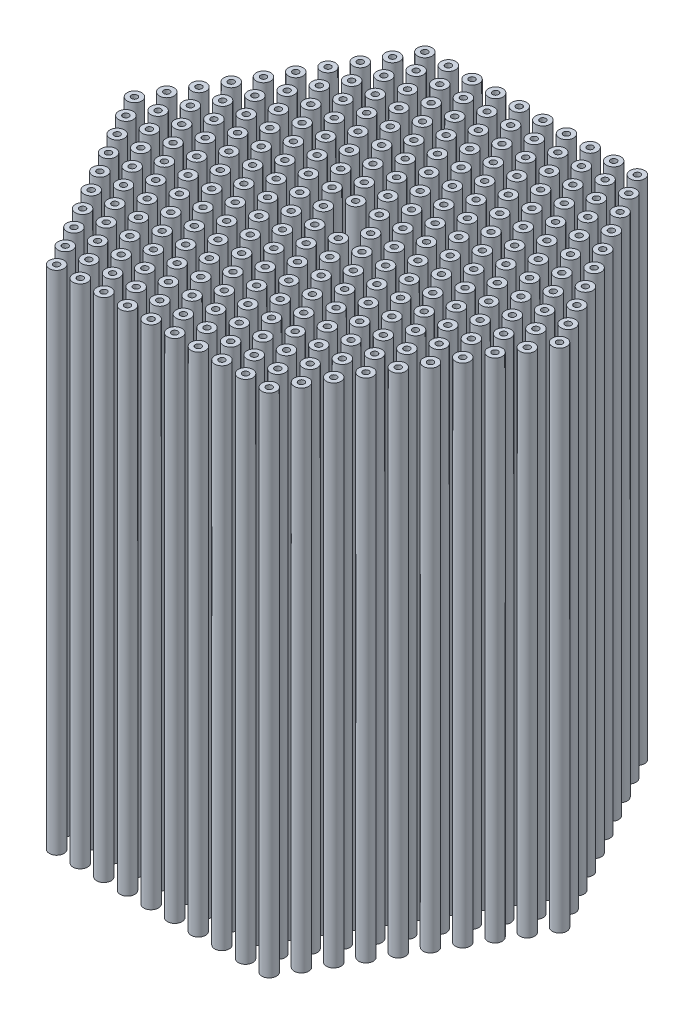
SolidWorks part; units mm, degrees
material "Chumbo puro"
ref_plane "Plano frontal" through (0, 0, 0) normal (0, 0, 1) x (1, 0, 0)
ref_plane "Plano superior" through (0, 0, 0) normal (0, 1, 0) x (1, 0, 0)
ref_plane "Plano direito" through (0, 0, 0) normal (1, 0, 0) x (0, 0, -1)
sketch "Esboço1" plane through (0, 0, 0) normal (0, 1, 0) x (1, 0, 0)
  line L0 (0, -642.4629) -> (0, 642.4629) construction
  line L1 (-577.4118, 0) -> (577.4118, 0) construction
  circle A0 centre (0, 0) radius 6.35 construction
  circle A1 centre (0, 0) radius 15.35 construction
  circle A2 centre (0, 0) radius 25 construction
  circle A23 centre (-25, 43.3013) radius 6.35
  circle A26 centre (-25, 43.3013) radius 15.35
  circle A29 centre (-25, 43.3013) radius 25 construction
  circle A50 centre (0, 86.6025) radius 6.35
  circle A53 centre (0, 86.6025) radius 15.35
  circle A56 centre (0, 86.6025) radius 25 construction
  circle A59 centre (-25, 129.9038) radius 6.35
  circle A62 centre (-25, 129.9038) radius 15.35
  circle A65 centre (-25, 129.9038) radius 25 construction
  circle A68 centre (25, 129.9038) radius 6.35
  circle A71 centre (25, 129.9038) radius 15.35
  circle A74 centre (25, 129.9038) radius 25 construction
  circle A77 centre (0, 173.2051) radius 6.35
  circle A80 centre (0, 173.2051) radius 15.35
  circle A83 centre (0, 173.2051) radius 25 construction
  circle A86 centre (-25, 216.5064) radius 6.35
  circle A87 centre (25, 43.3013) radius 6.35
  circle A88 centre (25, 43.3013) radius 15.35
  circle A89 centre (25, 43.3013) radius 25 construction
  circle A93 centre (-25, 216.5064) radius 15.35
  circle A94 centre (-25, 216.5064) radius 25 construction
  circle A95 centre (25, 216.5064) radius 6.35
  circle A96 centre (25, 216.5064) radius 15.35
  circle A97 centre (25, 216.5064) radius 25 construction
  circle A98 centre (0, 259.8076) radius 6.35
  circle A99 centre (0, 259.8076) radius 15.35
  circle A100 centre (0, 259.8076) radius 25 construction
  circle A101 centre (-25, 303.1089) radius 6.35
  circle A102 centre (-25, 303.1089) radius 15.35
  circle A103 centre (-25, 303.1089) radius 25 construction
  circle A104 centre (25, 303.1089) radius 6.35
  circle A105 centre (25, 303.1089) radius 15.35
  circle A106 centre (25, 303.1089) radius 25 construction
  circle A107 centre (0, 346.4102) radius 6.35
  circle A108 centre (0, 346.4102) radius 15.35
  circle A109 centre (0, 346.4102) radius 25 construction
  circle A110 centre (-25, 389.7114) radius 6.35
  circle A111 centre (-25, 389.7114) radius 15.35
  circle A112 centre (-25, 389.7114) radius 25 construction
  circle A113 centre (25, 389.7114) radius 6.35
  circle A114 centre (25, 389.7114) radius 15.35
  circle A115 centre (25, 389.7114) radius 25 construction
  circle A167 centre (50, 0) radius 15.35
  circle A168 centre (50, 0) radius 6.35
  circle A169 centre (100, 0) radius 15.35
  circle A170 centre (100, 0) radius 6.35
  circle A171 centre (150, 0) radius 15.35
  circle A172 centre (150, 0) radius 6.35
  circle A173 centre (200, 0) radius 15.35
  circle A174 centre (200, 0) radius 6.35
  circle A175 centre (250, 0) radius 15.35
  circle A176 centre (250, 0) radius 6.35
  circle A177 centre (300, 0) radius 15.35
  circle A178 centre (300, 0) radius 6.35
  circle A179 centre (350, 0) radius 15.35
  circle A180 centre (350, 0) radius 6.35
  circle A181 centre (400, 0) radius 15.35
  circle A182 centre (400, 0) radius 6.35
  circle A183 centre (450, 0) radius 15.35
  circle A184 centre (450, 0) radius 6.35
  circle A185 centre (-50, 0) radius 15.35
  circle A186 centre (-50, 0) radius 6.35
  circle A187 centre (-100, 0) radius 15.35
  circle A188 centre (-100, 0) radius 6.35
  circle A189 centre (-150, 0) radius 15.35
  circle A190 centre (-150, 0) radius 6.35
  circle A191 centre (-200, 0) radius 15.35
  circle A192 centre (-200, 0) radius 6.35
  circle A193 centre (-250, 0) radius 15.35
  circle A194 centre (-250, 0) radius 6.35
  circle A195 centre (-300, 0) radius 15.35
  circle A196 centre (-300, 0) radius 6.35
  circle A197 centre (-350, 0) radius 15.35
  circle A198 centre (-350, 0) radius 6.35
  circle A199 centre (-400, 0) radius 15.35
  circle A200 centre (-400, 0) radius 6.35
  circle A201 centre (-450, 0) radius 15.35
  circle A202 centre (-450, 0) radius 6.35
  circle A203 centre (75, 43.3013) radius 15.35
  circle A204 centre (75, 43.3013) radius 6.35
  circle A205 centre (125, 43.3013) radius 15.35
  circle A206 centre (125, 43.3013) radius 6.35
  circle A207 centre (175, 43.3013) radius 15.35
  circle A208 centre (175, 43.3013) radius 6.35
  circle A209 centre (225, 43.3013) radius 15.35
  circle A210 centre (225, 43.3013) radius 6.35
  circle A211 centre (275, 43.3013) radius 15.35
  circle A212 centre (275, 43.3013) radius 6.35
  circle A213 centre (325, 43.3013) radius 15.35
  circle A214 centre (325, 43.3013) radius 6.35
  circle A215 centre (375, 43.3013) radius 15.35
  circle A216 centre (375, 43.3013) radius 6.35
  circle A217 centre (425, 43.3013) radius 15.35
  circle A218 centre (425, 43.3013) radius 6.35
  circle A235 centre (50, 86.6025) radius 6.35
  circle A236 centre (50, 86.6025) radius 15.35
  circle A237 centre (100, 86.6025) radius 6.35
  circle A238 centre (100, 86.6025) radius 15.35
  circle A239 centre (150, 86.6025) radius 6.35
  circle A240 centre (150, 86.6025) radius 15.35
  circle A241 centre (200, 86.6025) radius 6.35
  circle A242 centre (200, 86.6025) radius 15.35
  circle A243 centre (250, 86.6025) radius 6.35
  circle A244 centre (250, 86.6025) radius 15.35
  circle A245 centre (300, 86.6025) radius 6.35
  circle A246 centre (300, 86.6025) radius 15.35
  circle A247 centre (350, 86.6025) radius 6.35
  circle A248 centre (350, 86.6025) radius 15.35
  circle A249 centre (400, 86.6025) radius 6.35
  circle A250 centre (400, 86.6025) radius 15.35
  circle A251 centre (75, 129.9038) radius 6.35
  circle A252 centre (75, 129.9038) radius 15.35
  circle A253 centre (125, 129.9038) radius 6.35
  circle A254 centre (125, 129.9038) radius 15.35
  circle A255 centre (175, 129.9038) radius 6.35
  circle A256 centre (175, 129.9038) radius 15.35
  circle A257 centre (225, 129.9038) radius 6.35
  circle A258 centre (225, 129.9038) radius 15.35
  circle A259 centre (275, 129.9038) radius 6.35
  circle A260 centre (275, 129.9038) radius 15.35
  circle A261 centre (325, 129.9038) radius 6.35
  circle A262 centre (325, 129.9038) radius 15.35
  circle A263 centre (375, 129.9038) radius 6.35
  circle A264 centre (375, 129.9038) radius 15.35
  circle A265 centre (50, 173.2051) radius 15.35
  circle A266 centre (50, 173.2051) radius 6.35
  circle A267 centre (100, 173.2051) radius 15.35
  circle A268 centre (100, 173.2051) radius 6.35
  circle A269 centre (150, 173.2051) radius 15.35
  circle A270 centre (150, 173.2051) radius 6.35
  circle A271 centre (200, 173.2051) radius 15.35
  circle A272 centre (200, 173.2051) radius 6.35
  circle A273 centre (250, 173.2051) radius 15.35
  circle A274 centre (250, 173.2051) radius 6.35
  circle A275 centre (300, 173.2051) radius 15.35
  circle A276 centre (300, 173.2051) radius 6.35
  circle A277 centre (350, 173.2051) radius 15.35
  circle A278 centre (350, 173.2051) radius 6.35
  circle A279 centre (75, 216.5064) radius 6.35
  circle A280 centre (75, 216.5064) radius 15.35
  circle A281 centre (125, 216.5064) radius 6.35
  circle A282 centre (125, 216.5064) radius 15.35
  circle A283 centre (175, 216.5064) radius 6.35
  circle A284 centre (175, 216.5064) radius 15.35
  circle A285 centre (225, 216.5064) radius 6.35
  circle A286 centre (225, 216.5064) radius 15.35
  circle A287 centre (275, 216.5064) radius 6.35
  circle A288 centre (275, 216.5064) radius 15.35
  circle A289 centre (325, 216.5064) radius 6.35
  circle A290 centre (325, 216.5064) radius 15.35
  circle A291 centre (50, 259.8076) radius 6.35
  circle A292 centre (50, 259.8076) radius 15.35
  circle A293 centre (100, 259.8076) radius 6.35
  circle A294 centre (100, 259.8076) radius 15.35
  circle A295 centre (150, 259.8076) radius 6.35
  circle A296 centre (150, 259.8076) radius 15.35
  circle A297 centre (200, 259.8076) radius 6.35
  circle A298 centre (200, 259.8076) radius 15.35
  circle A299 centre (250, 259.8076) radius 6.35
  circle A300 centre (250, 259.8076) radius 15.35
  circle A301 centre (300, 259.8076) radius 6.35
  circle A302 centre (300, 259.8076) radius 15.35
  circle A303 centre (75, 303.1089) radius 6.35
  circle A304 centre (75, 303.1089) radius 15.35
  circle A305 centre (125, 303.1089) radius 6.35
  circle A306 centre (125, 303.1089) radius 15.35
  circle A307 centre (175, 303.1089) radius 6.35
  circle A308 centre (175, 303.1089) radius 15.35
  circle A309 centre (225, 303.1089) radius 6.35
  circle A310 centre (225, 303.1089) radius 15.35
  circle A311 centre (275, 303.1089) radius 6.35
  circle A312 centre (275, 303.1089) radius 15.35
  circle A313 centre (50, 346.4102) radius 6.35
  circle A314 centre (50, 346.4102) radius 15.35
  circle A315 centre (100, 346.4102) radius 6.35
  circle A316 centre (100, 346.4102) radius 15.35
  circle A317 centre (150, 346.4102) radius 6.35
  circle A318 centre (150, 346.4102) radius 15.35
  circle A319 centre (200, 346.4102) radius 6.35
  circle A320 centre (200, 346.4102) radius 15.35
  circle A321 centre (250, 346.4102) radius 6.35
  circle A322 centre (250, 346.4102) radius 15.35
  circle A323 centre (75, 389.7114) radius 6.35
  circle A324 centre (75, 389.7114) radius 15.35
  circle A325 centre (125, 389.7114) radius 6.35
  circle A326 centre (125, 389.7114) radius 15.35
  circle A327 centre (175, 389.7114) radius 6.35
  circle A328 centre (175, 389.7114) radius 15.35
  circle A329 centre (225, 389.7114) radius 6.35
  circle A330 centre (225, 389.7114) radius 15.35
  circle A331 centre (-225, 389.7114) radius 15.35
  circle A332 centre (-225, 389.7114) radius 6.35
  circle A333 centre (-175, 389.7114) radius 15.35
  circle A334 centre (-175, 389.7114) radius 6.35
  circle A335 centre (-125, 389.7114) radius 15.35
  circle A336 centre (-125, 389.7114) radius 6.35
  circle A337 centre (-75, 389.7114) radius 15.35
  circle A338 centre (-75, 389.7114) radius 6.35
  circle A339 centre (-250, 346.4102) radius 15.35
  circle A340 centre (-250, 346.4102) radius 6.35
  circle A341 centre (-200, 346.4102) radius 15.35
  circle A342 centre (-200, 346.4102) radius 6.35
  circle A343 centre (-150, 346.4102) radius 15.35
  circle A344 centre (-150, 346.4102) radius 6.35
  circle A345 centre (-100, 346.4102) radius 15.35
  circle A346 centre (-100, 346.4102) radius 6.35
  circle A347 centre (-50, 346.4102) radius 15.35
  circle A348 centre (-50, 346.4102) radius 6.35
  circle A349 centre (-275, 303.1089) radius 15.35
  circle A350 centre (-275, 303.1089) radius 6.35
  circle A351 centre (-225, 303.1089) radius 15.35
  circle A352 centre (-225, 303.1089) radius 6.35
  circle A353 centre (-175, 303.1089) radius 15.35
  circle A354 centre (-175, 303.1089) radius 6.35
  circle A355 centre (-125, 303.1089) radius 15.35
  circle A356 centre (-125, 303.1089) radius 6.35
  circle A357 centre (-75, 303.1089) radius 15.35
  circle A358 centre (-75, 303.1089) radius 6.35
  circle A359 centre (-300, 259.8076) radius 15.35
  circle A360 centre (-300, 259.8076) radius 6.35
  circle A361 centre (-250, 259.8076) radius 15.35
  circle A362 centre (-250, 259.8076) radius 6.35
  circle A363 centre (-200, 259.8076) radius 15.35
  circle A364 centre (-200, 259.8076) radius 6.35
  circle A365 centre (-150, 259.8076) radius 15.35
  circle A366 centre (-150, 259.8076) radius 6.35
  circle A367 centre (-100, 259.8076) radius 15.35
  circle A368 centre (-100, 259.8076) radius 6.35
  circle A369 centre (-50, 259.8076) radius 15.35
  circle A370 centre (-50, 259.8076) radius 6.35
  circle A371 centre (-325, 216.5064) radius 15.35
  circle A372 centre (-325, 216.5064) radius 6.35
  circle A373 centre (-275, 216.5064) radius 15.35
  circle A374 centre (-275, 216.5064) radius 6.35
  circle A375 centre (-225, 216.5064) radius 15.35
  circle A376 centre (-225, 216.5064) radius 6.35
  circle A377 centre (-175, 216.5064) radius 15.35
  circle A378 centre (-175, 216.5064) radius 6.35
  circle A379 centre (-125, 216.5064) radius 15.35
  circle A380 centre (-125, 216.5064) radius 6.35
  circle A381 centre (-75, 216.5064) radius 15.35
  circle A382 centre (-75, 216.5064) radius 6.35
  circle A383 centre (-350, 173.2051) radius 6.35
  circle A384 centre (-350, 173.2051) radius 15.35
  circle A385 centre (-300, 173.2051) radius 6.35
  circle A386 centre (-300, 173.2051) radius 15.35
  circle A387 centre (-250, 173.2051) radius 6.35
  circle A388 centre (-250, 173.2051) radius 15.35
  circle A389 centre (-200, 173.2051) radius 6.35
  circle A390 centre (-200, 173.2051) radius 15.35
  circle A391 centre (-150, 173.2051) radius 6.35
  circle A392 centre (-150, 173.2051) radius 15.35
  circle A393 centre (-100, 173.2051) radius 6.35
  circle A394 centre (-100, 173.2051) radius 15.35
  circle A395 centre (-50, 173.2051) radius 6.35
  circle A396 centre (-50, 173.2051) radius 15.35
  circle A397 centre (-375, 129.9038) radius 15.35
  circle A398 centre (-375, 129.9038) radius 6.35
  circle A399 centre (-325, 129.9038) radius 15.35
  circle A400 centre (-325, 129.9038) radius 6.35
  circle A401 centre (-275, 129.9038) radius 15.35
  circle A402 centre (-275, 129.9038) radius 6.35
  circle A403 centre (-225, 129.9038) radius 15.35
  circle A404 centre (-225, 129.9038) radius 6.35
  circle A405 centre (-175, 129.9038) radius 15.35
  circle A406 centre (-175, 129.9038) radius 6.35
  circle A407 centre (-125, 129.9038) radius 15.35
  circle A408 centre (-125, 129.9038) radius 6.35
  circle A409 centre (-75, 129.9038) radius 15.35
  circle A410 centre (-75, 129.9038) radius 6.35
  circle A411 centre (-400, 86.6025) radius 15.35
  circle A412 centre (-400, 86.6025) radius 6.35
  circle A413 centre (-350, 86.6025) radius 15.35
  circle A414 centre (-350, 86.6025) radius 6.35
  circle A415 centre (-300, 86.6025) radius 15.35
  circle A416 centre (-300, 86.6025) radius 6.35
  circle A417 centre (-250, 86.6025) radius 15.35
  circle A418 centre (-250, 86.6025) radius 6.35
  circle A419 centre (-200, 86.6025) radius 15.35
  circle A420 centre (-200, 86.6025) radius 6.35
  circle A421 centre (-150, 86.6025) radius 15.35
  circle A422 centre (-150, 86.6025) radius 6.35
  circle A423 centre (-100, 86.6025) radius 15.35
  circle A424 centre (-100, 86.6025) radius 6.35
  circle A425 centre (-50, 86.6025) radius 15.35
  circle A426 centre (-50, 86.6025) radius 6.35
  circle A427 centre (-425, 43.3013) radius 6.35
  circle A428 centre (-425, 43.3013) radius 15.35
  circle A429 centre (-375, 43.3013) radius 6.35
  circle A430 centre (-375, 43.3013) radius 15.35
  circle A431 centre (-325, 43.3013) radius 6.35
  circle A432 centre (-325, 43.3013) radius 15.35
  circle A433 centre (-275, 43.3013) radius 6.35
  circle A434 centre (-275, 43.3013) radius 15.35
  circle A435 centre (-225, 43.3013) radius 6.35
  circle A436 centre (-225, 43.3013) radius 15.35
  circle A437 centre (-175, 43.3013) radius 6.35
  circle A438 centre (-175, 43.3013) radius 15.35
  circle A439 centre (-125, 43.3013) radius 6.35
  circle A440 centre (-125, 43.3013) radius 15.35
  circle A441 centre (-75, 43.3013) radius 6.35
  circle A442 centre (-75, 43.3013) radius 15.35
  circle A443 centre (-25, -43.3013) radius 25 construction
  circle A444 centre (25, -43.3013) radius 25 construction
  circle A445 centre (25, -389.7114) radius 25 construction
  circle A446 centre (-25, -389.7114) radius 25 construction
  circle A447 centre (0, -346.4102) radius 25 construction
  circle A448 centre (25, -303.1089) radius 25 construction
  circle A449 centre (-25, -303.1089) radius 25 construction
  circle A450 centre (0, -259.8076) radius 25 construction
  circle A451 centre (25, -216.5064) radius 25 construction
  circle A452 centre (-25, -216.5064) radius 25 construction
  circle A453 centre (0, -173.2051) radius 25 construction
  circle A454 centre (25, -129.9038) radius 25 construction
  circle A455 centre (-25, -129.9038) radius 25 construction
  circle A456 centre (0, -86.6025) radius 25 construction
  circle A457 centre (-75, -43.3013) radius 15.35
  circle A458 centre (-75, -43.3013) radius 6.35
  circle A459 centre (-125, -43.3013) radius 15.35
  circle A460 centre (-125, -43.3013) radius 6.35
  circle A461 centre (-175, -43.3013) radius 15.35
  circle A462 centre (-175, -43.3013) radius 6.35
  circle A463 centre (-225, -43.3013) radius 15.35
  circle A464 centre (-225, -43.3013) radius 6.35
  circle A465 centre (-275, -43.3013) radius 15.35
  circle A466 centre (-275, -43.3013) radius 6.35
  circle A467 centre (-325, -43.3013) radius 15.35
  circle A468 centre (-325, -43.3013) radius 6.35
  circle A469 centre (-375, -43.3013) radius 15.35
  circle A470 centre (-375, -43.3013) radius 6.35
  circle A471 centre (-425, -43.3013) radius 15.35
  circle A472 centre (-425, -43.3013) radius 6.35
  circle A473 centre (-50, -86.6025) radius 6.35
  circle A474 centre (-50, -86.6025) radius 15.35
  circle A475 centre (-100, -86.6025) radius 6.35
  circle A476 centre (-100, -86.6025) radius 15.35
  circle A477 centre (-150, -86.6025) radius 6.35
  circle A478 centre (-150, -86.6025) radius 15.35
  circle A479 centre (-200, -86.6025) radius 6.35
  circle A480 centre (-200, -86.6025) radius 15.35
  circle A481 centre (-250, -86.6025) radius 6.35
  circle A482 centre (-250, -86.6025) radius 15.35
  circle A483 centre (-300, -86.6025) radius 6.35
  circle A484 centre (-300, -86.6025) radius 15.35
  circle A485 centre (-350, -86.6025) radius 6.35
  circle A486 centre (-350, -86.6025) radius 15.35
  circle A487 centre (-400, -86.6025) radius 6.35
  circle A488 centre (-400, -86.6025) radius 15.35
  circle A489 centre (-75, -129.9038) radius 6.35
  circle A490 centre (-75, -129.9038) radius 15.35
  circle A491 centre (-125, -129.9038) radius 6.35
  circle A492 centre (-125, -129.9038) radius 15.35
  circle A493 centre (-175, -129.9038) radius 6.35
  circle A494 centre (-175, -129.9038) radius 15.35
  circle A495 centre (-225, -129.9038) radius 6.35
  circle A496 centre (-225, -129.9038) radius 15.35
  circle A497 centre (-275, -129.9038) radius 6.35
  circle A498 centre (-275, -129.9038) radius 15.35
  circle A499 centre (-325, -129.9038) radius 6.35
  circle A500 centre (-325, -129.9038) radius 15.35
  circle A501 centre (-375, -129.9038) radius 6.35
  circle A502 centre (-375, -129.9038) radius 15.35
  circle A503 centre (-50, -173.2051) radius 15.35
  circle A504 centre (-50, -173.2051) radius 6.35
  circle A505 centre (-100, -173.2051) radius 15.35
  circle A506 centre (-100, -173.2051) radius 6.35
  circle A507 centre (-150, -173.2051) radius 15.35
  circle A508 centre (-150, -173.2051) radius 6.35
  circle A509 centre (-200, -173.2051) radius 15.35
  circle A510 centre (-200, -173.2051) radius 6.35
  circle A511 centre (-250, -173.2051) radius 15.35
  circle A512 centre (-250, -173.2051) radius 6.35
  circle A513 centre (-300, -173.2051) radius 15.35
  circle A514 centre (-300, -173.2051) radius 6.35
  circle A515 centre (-350, -173.2051) radius 15.35
  circle A516 centre (-350, -173.2051) radius 6.35
  circle A517 centre (-75, -216.5064) radius 6.35
  circle A518 centre (-75, -216.5064) radius 15.35
  circle A519 centre (-125, -216.5064) radius 6.35
  circle A520 centre (-125, -216.5064) radius 15.35
  circle A521 centre (-175, -216.5064) radius 6.35
  circle A522 centre (-175, -216.5064) radius 15.35
  circle A523 centre (-225, -216.5064) radius 6.35
  circle A524 centre (-225, -216.5064) radius 15.35
  circle A525 centre (-275, -216.5064) radius 6.35
  circle A526 centre (-275, -216.5064) radius 15.35
  circle A527 centre (-325, -216.5064) radius 6.35
  circle A528 centre (-325, -216.5064) radius 15.35
  circle A529 centre (-50, -259.8076) radius 6.35
  circle A530 centre (-50, -259.8076) radius 15.35
  circle A531 centre (-100, -259.8076) radius 6.35
  circle A532 centre (-100, -259.8076) radius 15.35
  circle A533 centre (-150, -259.8076) radius 6.35
  circle A534 centre (-150, -259.8076) radius 15.35
  circle A535 centre (-200, -259.8076) radius 6.35
  circle A536 centre (-200, -259.8076) radius 15.35
  circle A537 centre (-250, -259.8076) radius 6.35
  circle A538 centre (-250, -259.8076) radius 15.35
  circle A539 centre (-300, -259.8076) radius 6.35
  circle A540 centre (-300, -259.8076) radius 15.35
  circle A541 centre (-75, -303.1089) radius 6.35
  circle A542 centre (-75, -303.1089) radius 15.35
  circle A543 centre (-125, -303.1089) radius 6.35
  circle A544 centre (-125, -303.1089) radius 15.35
  circle A545 centre (-175, -303.1089) radius 6.35
  circle A546 centre (-175, -303.1089) radius 15.35
  circle A547 centre (-225, -303.1089) radius 6.35
  circle A548 centre (-225, -303.1089) radius 15.35
  circle A549 centre (-275, -303.1089) radius 6.35
  circle A550 centre (-275, -303.1089) radius 15.35
  circle A551 centre (-50, -346.4102) radius 6.35
  circle A552 centre (-50, -346.4102) radius 15.35
  circle A553 centre (-100, -346.4102) radius 6.35
  circle A554 centre (-100, -346.4102) radius 15.35
  circle A555 centre (-150, -346.4102) radius 6.35
  circle A556 centre (-150, -346.4102) radius 15.35
  circle A557 centre (-200, -346.4102) radius 6.35
  circle A558 centre (-200, -346.4102) radius 15.35
  circle A559 centre (-250, -346.4102) radius 6.35
  circle A560 centre (-250, -346.4102) radius 15.35
  circle A561 centre (-75, -389.7114) radius 6.35
  circle A562 centre (-75, -389.7114) radius 15.35
  circle A563 centre (-125, -389.7114) radius 6.35
  circle A564 centre (-125, -389.7114) radius 15.35
  circle A565 centre (-175, -389.7114) radius 6.35
  circle A566 centre (-175, -389.7114) radius 15.35
  circle A567 centre (-225, -389.7114) radius 6.35
  circle A568 centre (-225, -389.7114) radius 15.35
  circle A569 centre (225, -389.7114) radius 15.35
  circle A570 centre (225, -389.7114) radius 6.35
  circle A571 centre (175, -389.7114) radius 15.35
  circle A572 centre (175, -389.7114) radius 6.35
  circle A573 centre (125, -389.7114) radius 15.35
  circle A574 centre (125, -389.7114) radius 6.35
  circle A575 centre (75, -389.7114) radius 15.35
  circle A576 centre (75, -389.7114) radius 6.35
  circle A577 centre (250, -346.4102) radius 15.35
  circle A578 centre (250, -346.4102) radius 6.35
  circle A579 centre (200, -346.4102) radius 15.35
  circle A580 centre (200, -346.4102) radius 6.35
  circle A581 centre (150, -346.4102) radius 15.35
  circle A582 centre (150, -346.4102) radius 6.35
  circle A583 centre (100, -346.4102) radius 15.35
  circle A584 centre (100, -346.4102) radius 6.35
  circle A585 centre (50, -346.4102) radius 15.35
  circle A586 centre (50, -346.4102) radius 6.35
  circle A587 centre (275, -303.1089) radius 15.35
  circle A588 centre (275, -303.1089) radius 6.35
  circle A589 centre (225, -303.1089) radius 15.35
  circle A590 centre (225, -303.1089) radius 6.35
  circle A591 centre (175, -303.1089) radius 15.35
  circle A592 centre (175, -303.1089) radius 6.35
  circle A593 centre (125, -303.1089) radius 15.35
  circle A594 centre (125, -303.1089) radius 6.35
  circle A595 centre (75, -303.1089) radius 15.35
  circle A596 centre (75, -303.1089) radius 6.35
  circle A597 centre (300, -259.8076) radius 15.35
  circle A598 centre (300, -259.8076) radius 6.35
  circle A599 centre (250, -259.8076) radius 15.35
  circle A600 centre (250, -259.8076) radius 6.35
  circle A601 centre (200, -259.8076) radius 15.35
  circle A602 centre (200, -259.8076) radius 6.35
  circle A603 centre (150, -259.8076) radius 15.35
  circle A604 centre (150, -259.8076) radius 6.35
  circle A605 centre (100, -259.8076) radius 15.35
  circle A606 centre (100, -259.8076) radius 6.35
  circle A607 centre (50, -259.8076) radius 15.35
  circle A608 centre (50, -259.8076) radius 6.35
  circle A609 centre (325, -216.5064) radius 15.35
  circle A610 centre (325, -216.5064) radius 6.35
  circle A611 centre (275, -216.5064) radius 15.35
  circle A612 centre (275, -216.5064) radius 6.35
  circle A613 centre (225, -216.5064) radius 15.35
  circle A614 centre (225, -216.5064) radius 6.35
  circle A615 centre (175, -216.5064) radius 15.35
  circle A616 centre (175, -216.5064) radius 6.35
  circle A617 centre (125, -216.5064) radius 15.35
  circle A618 centre (125, -216.5064) radius 6.35
  circle A619 centre (75, -216.5064) radius 15.35
  circle A620 centre (75, -216.5064) radius 6.35
  circle A621 centre (350, -173.2051) radius 6.35
  circle A622 centre (350, -173.2051) radius 15.35
  circle A623 centre (300, -173.2051) radius 6.35
  circle A624 centre (300, -173.2051) radius 15.35
  circle A625 centre (250, -173.2051) radius 6.35
  circle A626 centre (250, -173.2051) radius 15.35
  circle A627 centre (200, -173.2051) radius 6.35
  circle A628 centre (200, -173.2051) radius 15.35
  circle A629 centre (150, -173.2051) radius 6.35
  circle A630 centre (150, -173.2051) radius 15.35
  circle A631 centre (100, -173.2051) radius 6.35
  circle A632 centre (100, -173.2051) radius 15.35
  circle A633 centre (50, -173.2051) radius 6.35
  circle A634 centre (50, -173.2051) radius 15.35
  circle A635 centre (375, -129.9038) radius 15.35
  circle A636 centre (375, -129.9038) radius 6.35
  circle A637 centre (325, -129.9038) radius 15.35
  circle A638 centre (325, -129.9038) radius 6.35
  circle A639 centre (275, -129.9038) radius 15.35
  circle A640 centre (275, -129.9038) radius 6.35
  circle A641 centre (225, -129.9038) radius 15.35
  circle A642 centre (225, -129.9038) radius 6.35
  circle A643 centre (175, -129.9038) radius 15.35
  circle A644 centre (175, -129.9038) radius 6.35
  circle A645 centre (125, -129.9038) radius 15.35
  circle A646 centre (125, -129.9038) radius 6.35
  circle A647 centre (75, -129.9038) radius 15.35
  circle A648 centre (75, -129.9038) radius 6.35
  circle A649 centre (400, -86.6025) radius 15.35
  circle A650 centre (400, -86.6025) radius 6.35
  circle A651 centre (350, -86.6025) radius 15.35
  circle A652 centre (350, -86.6025) radius 6.35
  circle A653 centre (300, -86.6025) radius 15.35
  circle A654 centre (300, -86.6025) radius 6.35
  circle A655 centre (250, -86.6025) radius 15.35
  circle A656 centre (250, -86.6025) radius 6.35
  circle A657 centre (200, -86.6025) radius 15.35
  circle A658 centre (200, -86.6025) radius 6.35
  circle A659 centre (150, -86.6025) radius 15.35
  circle A660 centre (150, -86.6025) radius 6.35
  circle A661 centre (100, -86.6025) radius 15.35
  circle A662 centre (100, -86.6025) radius 6.35
  circle A663 centre (50, -86.6025) radius 15.35
  circle A664 centre (50, -86.6025) radius 6.35
  circle A665 centre (425, -43.3013) radius 6.35
  circle A666 centre (425, -43.3013) radius 15.35
  circle A667 centre (375, -43.3013) radius 6.35
  circle A668 centre (375, -43.3013) radius 15.35
  circle A669 centre (325, -43.3013) radius 6.35
  circle A670 centre (325, -43.3013) radius 15.35
  circle A671 centre (275, -43.3013) radius 6.35
  circle A672 centre (275, -43.3013) radius 15.35
  circle A673 centre (225, -43.3013) radius 6.35
  circle A674 centre (225, -43.3013) radius 15.35
  circle A675 centre (175, -43.3013) radius 6.35
  circle A676 centre (175, -43.3013) radius 15.35
  circle A677 centre (125, -43.3013) radius 6.35
  circle A678 centre (125, -43.3013) radius 15.35
  circle A679 centre (75, -43.3013) radius 6.35
  circle A680 centre (75, -43.3013) radius 15.35
  circle A681 centre (25, -389.7114) radius 15.35
  circle A682 centre (25, -389.7114) radius 6.35
  circle A683 centre (-25, -389.7114) radius 15.35
  circle A684 centre (-25, -389.7114) radius 6.35
  circle A685 centre (0, -346.4102) radius 15.35
  circle A686 centre (0, -346.4102) radius 6.35
  circle A687 centre (25, -303.1089) radius 15.35
  circle A688 centre (25, -303.1089) radius 6.35
  circle A689 centre (-25, -303.1089) radius 15.35
  circle A690 centre (-25, -303.1089) radius 6.35
  circle A691 centre (0, -259.8076) radius 15.35
  circle A692 centre (0, -259.8076) radius 6.35
  circle A693 centre (25, -216.5064) radius 15.35
  circle A694 centre (25, -216.5064) radius 6.35
  circle A695 centre (-25, -216.5064) radius 15.35
  circle A696 centre (25, -43.3013) radius 15.35
  circle A697 centre (25, -43.3013) radius 6.35
  circle A698 centre (-25, -216.5064) radius 6.35
  circle A699 centre (0, -173.2051) radius 15.35
  circle A700 centre (0, -173.2051) radius 6.35
  circle A701 centre (25, -129.9038) radius 15.35
  circle A702 centre (25, -129.9038) radius 6.35
  circle A703 centre (-25, -129.9038) radius 15.35
  circle A704 centre (-25, -129.9038) radius 6.35
  circle A705 centre (0, -86.6025) radius 15.35
  circle A706 centre (0, -86.6025) radius 6.35
  circle A707 centre (-25, -43.3013) radius 15.35
  circle A708 centre (-25, -43.3013) radius 6.35
  point P13 (0, 0)
  dimension "D1" = 12.7
  dimension "D2" = 30.7
  dimension "D3" = 50
  dimension "D4" = 50
  dimension "D5" = 50
  dimension "D6" = 50
  dimension "D7" = 50
  dimension "D11" = 50
  dimension "D12" = 50
  dimension "D13" = 50
  dimension "D14" = 50
  dimension "D15" = 50
  dimension "D90" = 50
  dimension "D91" = 50
  dimension "D88" = 10
  dimension "D89" = 10
  dimension "D92" = 9
  dimension "D94" = 9
  dimension "D95" = 8
  dimension "D96" = 8
  dimension "D97" = 7
  dimension "D98" = 7
  dimension "D99" = 6
  dimension "D100" = 6
  dimension "D101" = 5
extrude "Ressalto-extrusão1" add sketch "Esboço1" along normal blind 1072.5
